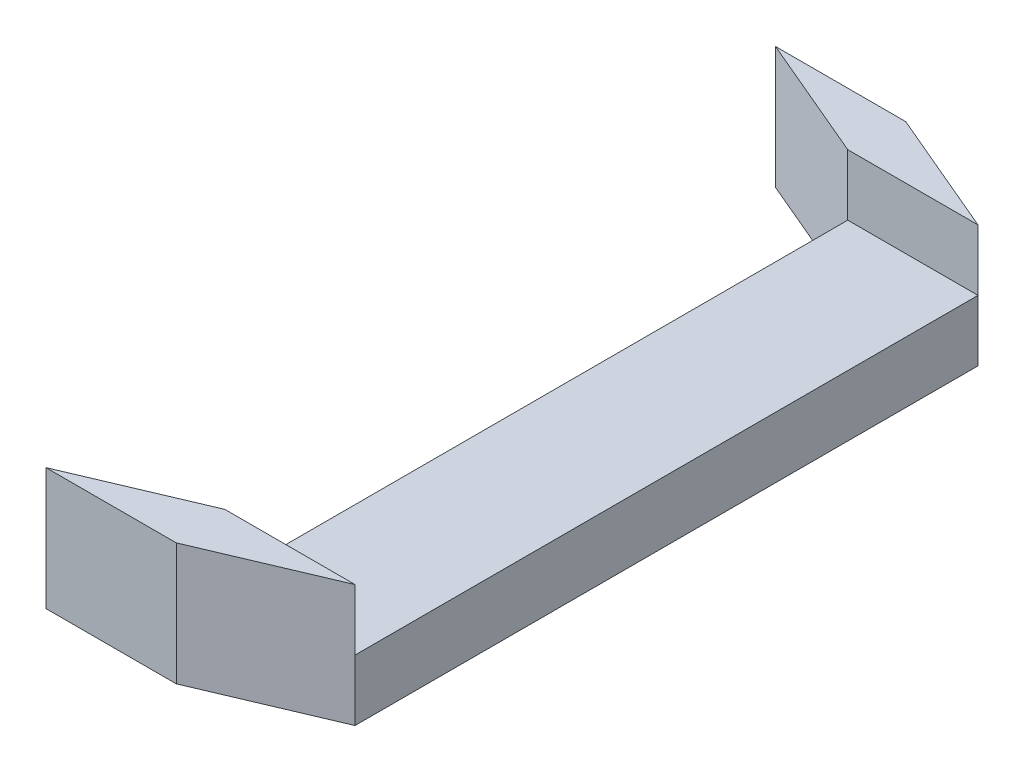
SolidWorks part; units mm, degrees
ref_plane "Front Plane" through (0, 0, 0) normal (0, 0, 1) x (1, 0, 0)
ref_plane "Top Plane" through (0, 0, 0) normal (0, 1, 0) x (1, 0, 0)
ref_plane "Right Plane" through (0, 0, 0) normal (1, 0, 0) x (0, 0, -1)
sketch "Sketch1" plane through (0, 0, 0) normal (0, 1, 0) x (1, 0, 0)
  line L0 (3.2, 15.305) -> (-3.2, 15.305)
  line L1 (-3.2, 15.305) -> (3.2, 15.305)
  line L2 (-3.2, 15.305) -> (-3.2, -15.305)
  line L3 (-3.2, -15.305) -> (3.2, -15.305)
  line L4 (3.2, 15.305) -> (3.2, -15.305)
  line L5 (-3.2, 15.305) -> (3.2, -15.305) construction
  line L6 (-3.2, -15.305) -> (3.2, 15.305) construction
  line L7 (3.2, 15.305) -> (-2.9662, 17.9224)
  line L8 (-3.2, 15.305) -> (-9.3662, 17.9224)
  line L9 (-2.9662, 17.9224) -> (-9.3662, 17.9224)
  line L10 (-6.7706, 0) -> (6.7706, 0) construction
  line L11 (-3.2, -15.305) -> (-9.3662, -17.9224)
  line L12 (-2.9662, -17.9224) -> (-9.3662, -17.9224)
  line L13 (3.2, -15.305) -> (-2.9662, -17.9224)
  line L14 (3.2, -15.305) -> (-3.2, -15.305)
  point P0 (0, 0)
  dimension "D1" = 30.61
  dimension "D2" = 23
  dimension "D3" = 6.4
extrude "Boss-Extrude1" add sketch "Sketch1" along normal blind 3 contours L4 L0 L2 L3 region at (0, 0, 0)
extrude "Boss-Extrude2" add sketch "Sketch1<3>" along normal blind 6 contours L13 L3 L11 L12 | L7 L9 L8 L0 region at (-3.0831, 0, -16.6137) region at (-3.0831, 0, 16.6137)
sketch "Sketch1<3>" plane through (0, 0, 0) normal (0, 1, 0) x (1, 0, 0) same geometry as "Sketch1"
